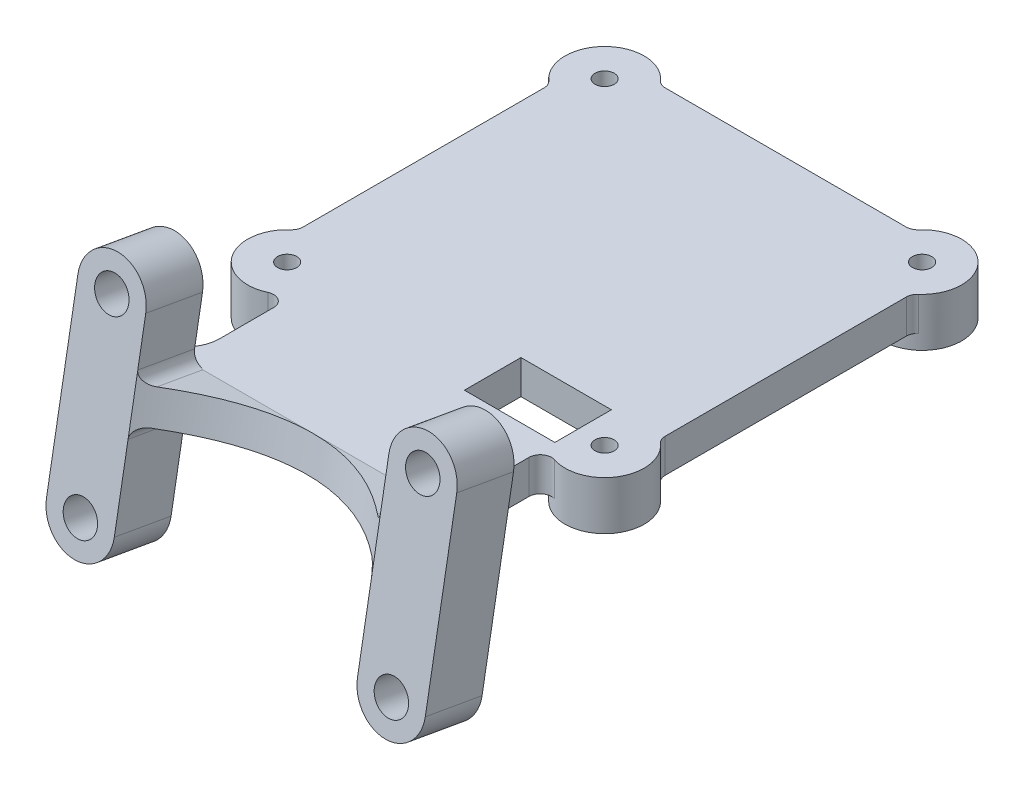
SolidWorks part; units mm, degrees
ref_plane "Front Plane" through (0, 0, 0) normal (0, 0, 1) x (1, 0, 0)
ref_plane "Top Plane" through (0, 0, 0) normal (0, 1, 0) x (1, 0, 0)
ref_plane "Right Plane" through (0, 0, 0) normal (1, 0, 0) x (0, 0, -1)
sketch "Sketch1" plane through (0, 0, 0) normal (0, 1, 0) x (1, 0, 0)
  line L0 (-16.0143, 16.0143) -> (-16.0143, 11.1488) construction
  line L1 (11.1488, 16.0143) -> (-11.1488, 16.0143)
  line L2 (16.0143, 11.1488) -> (16.0143, -11.1488)
  line L4 (-16.0143, 11.1488) -> (-16.0143, -11.1488)
  line L5 (16.0143, 16.0143) -> (-16.0143, -16.0143) construction
  line L6 (15.9857, -15.9857) -> (-16.0143, 16.0143) construction
  line L7 (-16.0143, 16.0143) -> (-11.1488, 16.0143) construction
  line L8 (16.0143, 16.0143) -> (16.0143, 11.0332) construction
  line L9 (16.0143, 16.0143) -> (11.1488, 16.0143) construction
  line L10 (15.9857, -15.9857) -> (11.6143, -15.9857) construction
  line L11 (15.9857, -15.9857) -> (16.0143, -11.1488) construction
  line L12 (-16.0143, -16.0143) -> (-16.0143, -11.1488) construction
  line L15 (11.6143, -11.0143) -> (3.6143, -11.0143)
  line L16 (11.6143, -11.0143) -> (11.6143, -15.9857)
  line L18 (3.6143, -11.0143) -> (3.6143, -16.0143)
  line L19 (11.6143, -11.0143) -> (3.6143, -16.0143) construction
  line L20 (11.6143, -15.9857) -> (3.6143, -11.0143) construction
  line L21 (11.6143, -15.9857) -> (11.6143, -16.0143)
  line L22 (-11.1488, -26.0143) -> (11.6143, -26.0143)
  line L23 (-11.1488, -26.0143) -> (-11.1488, -16.0143)
  line L24 (3.6143, -16.0143) -> (11.6143, -16.0143)
  line L25 (11.6143, -26.0143) -> (11.6143, -16.5629)
  line L26 (-11.1488, -26.0143) -> (11.6143, -16.0143) construction
  line L27 (-11.1488, -16.0143) -> (11.6143, -26.0143) construction
  circle A0 centre (14.0361, 14.0361) radius 0.85
  circle A1 centre (14.0361, -14.0361) radius 0.85
  circle A2 centre (-14.0361, -14.0361) radius 0.85
  circle A3 centre (-14.0361, 14.0361) radius 0.85
  arc A4 (-11.1488, 16.0143) -> (-16.0143, 11.1488) centre (-14.0361, 14.0361) ccw
  arc A5 (16.0143, 11.1488) -> (11.1488, 16.0143) centre (14.0361, 14.0361) ccw
  arc A6 (11.6143, -16.5629) -> (16.0143, -11.1488) centre (14.0361, -14.0361) ccw
  arc A7 (-16.0143, -11.1488) -> (-11.1488, -16.0143) centre (-14.0361, -14.0361) ccw
  point P0 (0, 0)
  point P3 (0.2328, -21.0143)
  point P8 (-13.435, -13.435)
  point P9 (13.435, 13.435)
  point P20 (7.6258, -13.5071)
  point P31 (0, 0)
  point P51 (0, 0)
  dimension "D3" = 1.7
  dimension "D5" = 3.5
  dimension "D7" = 10
  dimension "D1" = 32
  dimension "D4" = 39.7
  dimension "D8" = 12.4
  dimension "D9" = 8
  dimension "D10" = 5
  dimension "D2" = 45.2953
  dimension "D6" = 4
extrude "Boss-Extrude1" add sketch "Sketch1" along normal blind 2.9967
ref_plane "Plane1" through (0.2328, 0, 0) normal (1, 0, 0) x (0, 0, -1)
sketch "Sketch4" plane through (0, 0, 0) normal (0, -1, 0) x (1, 0, 0)
  line L3 (11.6143, 11.5092) -> (11.6143, 16.5629)
  circle A0 centre (-14.0361, -14.0361) radius 0.85 construction
  circle A1 centre (14.0361, -14.0361) radius 0.85 construction
  circle A2 centre (14.0361, 14.0361) radius 0.85 construction
  circle A3 centre (-14.0361, 14.0361) radius 0.85 construction
  circle A4 centre (-14.0361, -14.0361) radius 0.85
  circle A5 centre (14.0361, -14.0361) radius 0.85
  circle A6 centre (14.0361, 14.0361) radius 0.85
  circle A7 centre (-14.0361, 14.0361) radius 0.85
  circle A8 centre (-14.0361, 14.0361) radius 3.5
  arc A9 (11.6143, 11.5092) -> (11.6143, 16.5629) centre (14.0361, 14.0361) ccw
  circle A10 centre (14.0361, -14.0361) radius 3.5
  circle A11 centre (-14.0361, -14.0361) radius 3.5
extrude "Boss-Extrude3" add sketch "Sketch4" along normal blind 1.3
ref_plane "Plane3" through (0, 4.5391, 25.7423) normal (0, 0.1736, 0.9848) x (1, 0, 0)
sketch "Sketch7" plane through (0, 4.5391, 25.7423) normal (0, 0.1736, 0.9848) x (1, 0, 0)
  line L0 (0.2328, 1.4838) -> (0.2328, -10.5185) construction
  line L1 (0.2328, -4.5173) -> (-16.5172, -4.5173) construction
  line L2 (-10.5172, 3.4827) -> (-10.5172, -1.5662)
  line L3 (-16.5172, 3.4827) -> (-16.5172, -12.5173)
  line L4 (10.9828, 3.4827) -> (10.9828, -1.5662)
  line L5 (16.9828, 3.4827) -> (16.9828, -12.5173)
  line L6 (-11.1488, -4.5173) -> (11.6143, -4.5173) construction
  line L7 (-10.5172, -4.5173) -> (10.9828, -4.5173)
  line L8 (-10.5172, -1.5662) -> (10.9828, -1.5662)
  line L9 (10.9828, -4.5173) -> (10.9828, -12.5173)
  line L10 (-10.5172, -4.5173) -> (-10.5172, -12.5173)
  line L11 (-11.1488, -1.5662) -> (11.6143, -1.5662) construction
  line L12 (0.2328, -1.6482) -> (0.2328, 1.6482) construction
  circle A0 centre (-13.5172, 3.4827) radius 1.5
  arc A1 (-10.5172, 3.4827) -> (-16.5172, 3.4827) centre (-13.5172, 3.4827) ccw
  circle A2 centre (-13.5172, -12.5173) radius 1.5
  arc A3 (-10.5172, -12.5173) -> (-16.5172, -12.5173) centre (-13.5172, -12.5173) cw
  circle A4 centre (13.9828, -12.5173) radius 1.5
  arc A5 (10.9828, 3.4827) -> (16.9828, 3.4827) centre (13.9828, 3.4827) cw
  arc A6 (10.9828, -12.5173) -> (16.9828, -12.5173) centre (13.9828, -12.5173) ccw
  circle A7 centre (13.9828, 3.4827) radius 1.5
  point P10 (-16.5172, -4.5173)
  point P15 (-12.25, -4.5173)
  dimension "D1" = 3
  dimension "D2" = 1.5
  dimension "D3" = 27.5
  dimension "D4" = 16
extrude "Boss-Extrude5" add sketch "Sketch7" along normal blind 5 and the other way blind 0.1
sketch "Sketch9" plane through (0, -4.4487, 0.7844) normal (0, -0.9848, 0.1736) x (1, 0, 0)
  line L0 (-9.7672, 31.1394) -> (-9.7672, 26.1394) construction
  line L1 (-10.5172, 31.1394) -> (10.9828, 31.1394) construction
  line L2 (-9.7672, 26.1394) -> (10.2328, 26.1394) construction
  line L3 (0.2328, 26.1394) -> (0.2328, 31.1394) construction
  line L4 (10.2328, 31.1394) -> (10.2328, 26.1394) construction
  line L5 (-9.7672, 31.1394) -> (10.2328, 31.1394) construction
  line L6 (-10.5172, 31.1394) -> (10.9828, 31.1394)
  spline S0 degree 2 poles (-10.5172, 31.1394) (0.2328, 21.1394) (10.9828, 31.1394) knots 0 0 0 1 1 1
  dimension "D1" = 5
  dimension "D2" = 20
extrude "Cut-Extrude4" cut sketch "Sketch9" against normal through all both and the other way through all
fillet "Fillet3" radius 3 2 edges at (-11.1488, 2.7087, 25.9635) (11.6143, 2.7087, 25.9635)
fillet "Fillet4" radius 1 12 edges at (-16.0143, 1.4983, 11.1488) (-16.0143, 1.4983, -11.1488) (11.1488, 1.4983, -16.0143) (16.0143, 1.4983, -11.1488) (-11.1488, 1.4983, -16.0143) (16.0143, 1.4983, 11.1488) (11.6143, 1.4983, 16.5629) (-11.1488, 1.4983, 16.0143) (10.9828, 3.4308, 28.4763) (-10.5172, 3.4308, 28.4763) (10.9828, 0.5158, 28.9395) (-10.5172, 0.5158, 28.9395)
